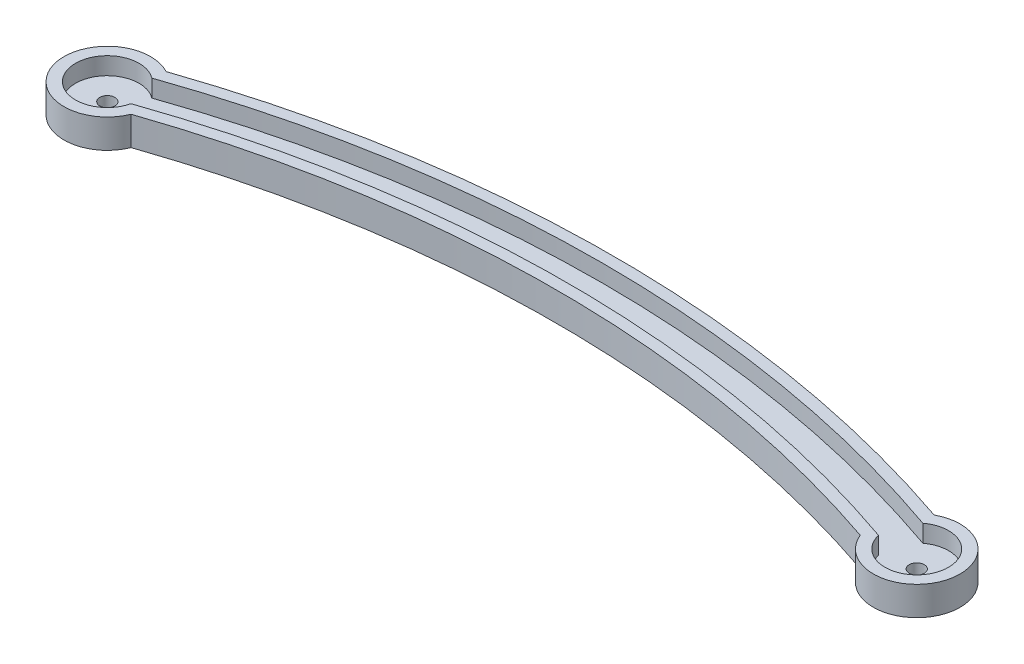
SolidWorks part; units mm, degrees
material "PLA"
ref_plane "Płaszczyzna przednia" through (0, 0, 0) normal (0, 0, 1) x (1, 0, 0)
ref_plane "Blat stołu" through (0, 0, 0) normal (0, 1, 0) x (1, 0, 0)
ref_plane "Płaszczyzna prawa" through (0, 0, 0) normal (1, 0, 0) x (0, 0, -1)
sketch "Szkic4" plane through (0, 0, 0) normal (0, 1, 0) x (1, 0, 0)
  arc A0 (3.5785, 6.5912) -> (6.9475, -2.8252) centre (0, 0) ccw
  arc A1 (133.0525, -2.8252) -> (136.4215, 6.5912) centre (140, 0) ccw
  arc A2 (0, 0) -> (140, 0) centre (70, -187.3499) cw construction
  arc A3 (6.9475, -2.8252) -> (133.0525, -2.8252) centre (70, -187.3499) cw
  arc A4 (3.5785, 6.5912) -> (136.4215, 6.5912) centre (70, -187.3499) cw
  arc A6 (-1.75, 4.6837) -> (141.75, 4.6837) centre (70, -187.3499) cw construction
  arc A7 (1.75, -4.6837) -> (138.25, -4.6837) centre (70, -187.3499) cw construction
  dimension "D2" = 15
  dimension "D3" = 15
  dimension "D4" = 200
  dimension "D1" = 140
  dimension "D5" = 70
  dimension "D6" = 5
  dimension "D7" = 5
extrude "Dodanie-wyciągnięcie2" add sketch "Szkic4" along normal blind 5
shell "Skorupa2" thickness 2 removed face at (70, 5, -5.0618)
hole_wizard "Otwór pod śrubę M22" positions "Szkic 3D2" profile "Szkic5" hole size "M2" standard "ISO" end condition up to next
sketch3d "Szkic 3D2"
  line L0 (0, 5, 0) -> (0, 2, 0) construction
  line L1 (0, 5, 0) -> (0, 0, 0) construction
  arc A0 (134.646, 2, 1.2588) -> (136.6812, 2, -4.3859) centre (140, 2, 0) ccw construction
  arc A1 (3.3188, 5, -4.3859) -> (5.354, 5, 1.2588) centre (0, 5, 0) ccw construction
  point P0 (0, 0, 0)
  point P3 (0, 0, 0)
  point P5 (140, 2, 0)
  point P7 (0, 0, 0)
  point P13 (140, 7.5, 0)
  point P14 (0, 10, 0)
  point P20 (0, 10, 0)
  point P22 (0, 10, 0)
  point P25 (0, 0, 0)
  point P27 (0, 2, 0)
  point P33 (0, 10.5, 0)
sketch "Szkic5" plane through (0, 2, 0) normal (1, 0, 0) x (0, 0, 1)
  line L0 (0, 0) -> (0, 2.001)
  line L1 (0, 2.001) -> (1.3, 2.001)
  line L2 (1.3, 2.001) -> (1.3, 0)
  line L5 (1.3, 0) -> (0, 0)
  line L11 (0, -6.35) -> (0, 107.95) construction
  dimension "Średnica otworu na wylot" = 2.6
  dimension "Głębokość otworu na wylot" = 2.001
